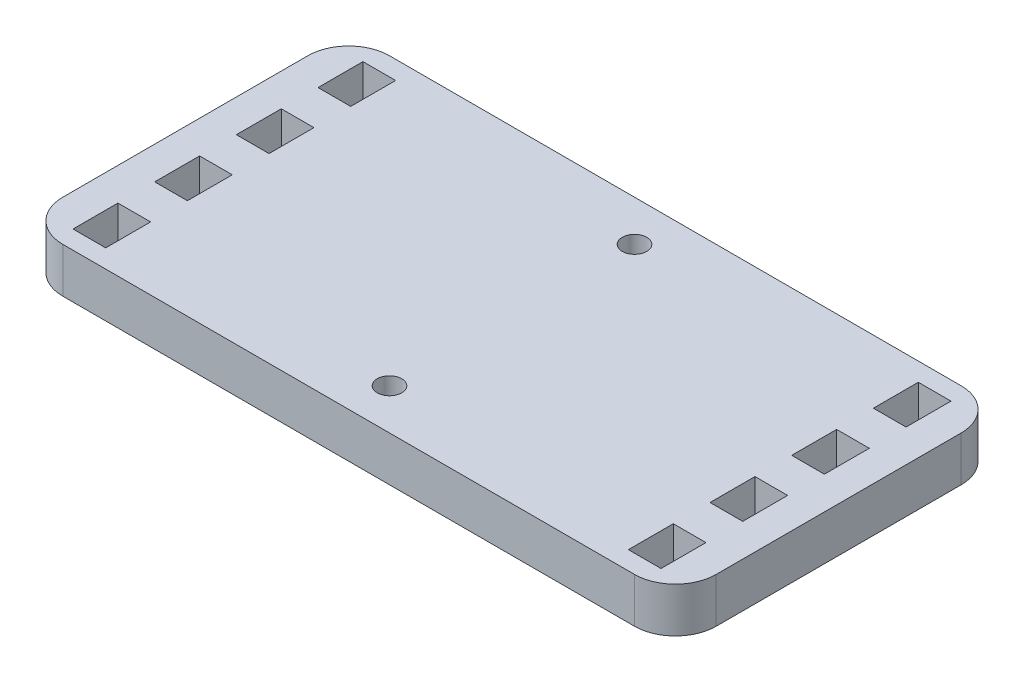
SolidWorks part; units mm, degrees
ref_plane "Front Plane" through (0, 0, 0) normal (0, 0, 1) x (1, 0, 0)
ref_plane "Top Plane" through (0, 0, 0) normal (0, 1, 0) x (1, 0, 0)
ref_plane "Right Plane" through (0, 0, 0) normal (1, 0, 0) x (0, 0, -1)
sketch "Sketch1" plane through (0, 0, 0) normal (0, 1, 0) x (1, 0, 0)
  line L1 (40, -20) -> (-40, -20)
  line L2 (40, -20) -> (40, 20)
  line L3 (40, 20) -> (-40, 20)
  line L4 (-40, -20) -> (-40, 20)
  line L5 (40, -20) -> (-40, 20) construction
  line L6 (40, 20) -> (-40, -20) construction
  circle A0 centre (0, 15) radius 1.5
  circle A1 centre (0, -15) radius 1.5
  point P0 (0, 0)
  point P10 (0, 0)
  point P11 (0, 0)
  dimension "D3" = 15
  dimension "D4" = 3
  dimension "D1" = 80
  dimension "D2" = 40
  dimension "15mm" = 15
extrude "Boss-Extrude1" add sketch "Sketch1" along normal blind 5.5
sketch "Sketch2" plane through (0, 5.5, 0) normal (0, 1, 0) x (1, 0, 0)
  line L1 (40, 20) -> (-40, 20) construction
  line L2 (-40, -20) -> (40, -20) construction
  line L3 (0, 20) -> (0, -20) construction
  line L4 (-34, 20) -> (-34, -20) construction
  line L5 (-40, 20) -> (-40, -20) construction
  line L6 (-32, 7.75) -> (-32, 2.25)
  line L7 (-36, 17.75) -> (-32, 17.75)
  line L8 (-36, 17.75) -> (-36, 12.25)
  line L9 (-36, 12.25) -> (-32, 12.25)
  line L10 (-32, 17.75) -> (-32, 12.25)
  line L11 (-36, 17.75) -> (-32, 12.25) construction
  line L12 (-36, 12.25) -> (-32, 17.75) construction
  line L13 (-36, 7.75) -> (-32, 7.75)
  line L14 (-36, 7.75) -> (-36, 2.25)
  line L15 (-36, 2.25) -> (-32, 2.25)
  line L16 (-32, -2.25) -> (-32, -7.75)
  line L17 (-36, -2.25) -> (-32, -2.25)
  line L18 (-36, -2.25) -> (-36, -7.75)
  line L19 (-36, -7.75) -> (-32, -7.75)
  line L20 (-32, -12.25) -> (-32, -17.75)
  line L21 (-36, -12.25) -> (-32, -12.25)
  line L22 (-36, -12.25) -> (-36, -17.75)
  line L23 (-36, -17.75) -> (-32, -17.75)
  line L24 (36, -17.75) -> (32, -17.75)
  line L25 (32, -12.25) -> (32, -17.75)
  line L26 (36, -12.25) -> (36, -17.75)
  line L27 (36, -12.25) -> (32, -12.25)
  line L28 (36, 17.75) -> (32, 17.75)
  line L29 (32, 17.75) -> (32, 12.25)
  line L30 (36, 12.25) -> (32, 12.25)
  line L31 (36, 17.75) -> (36, 12.25)
  line L32 (36, -7.75) -> (32, -7.75)
  line L33 (32, -2.25) -> (32, -7.75)
  line L34 (36, -2.25) -> (36, -7.75)
  line L35 (36, -2.25) -> (32, -2.25)
  line L36 (36, 2.25) -> (32, 2.25)
  line L37 (32, 7.75) -> (32, 2.25)
  line L38 (36, 7.75) -> (36, 2.25)
  line L39 (36, 7.75) -> (32, 7.75)
  point P13 (-34, 15)
  dimension "D1" = 6
  dimension "D2" = 5
  dimension "D3" = 5.5
  dimension "D4" = 4
  dimension "D5" = 4
extrude "Cut-Extrude1" cut sketch "Sketch2" against normal through all
fillet "Fillet1" radius 5 4 edges at (40, 2.75, -20) (-40, 2.75, -20) (-40, 2.75, 20) (40, 2.75, 20)
